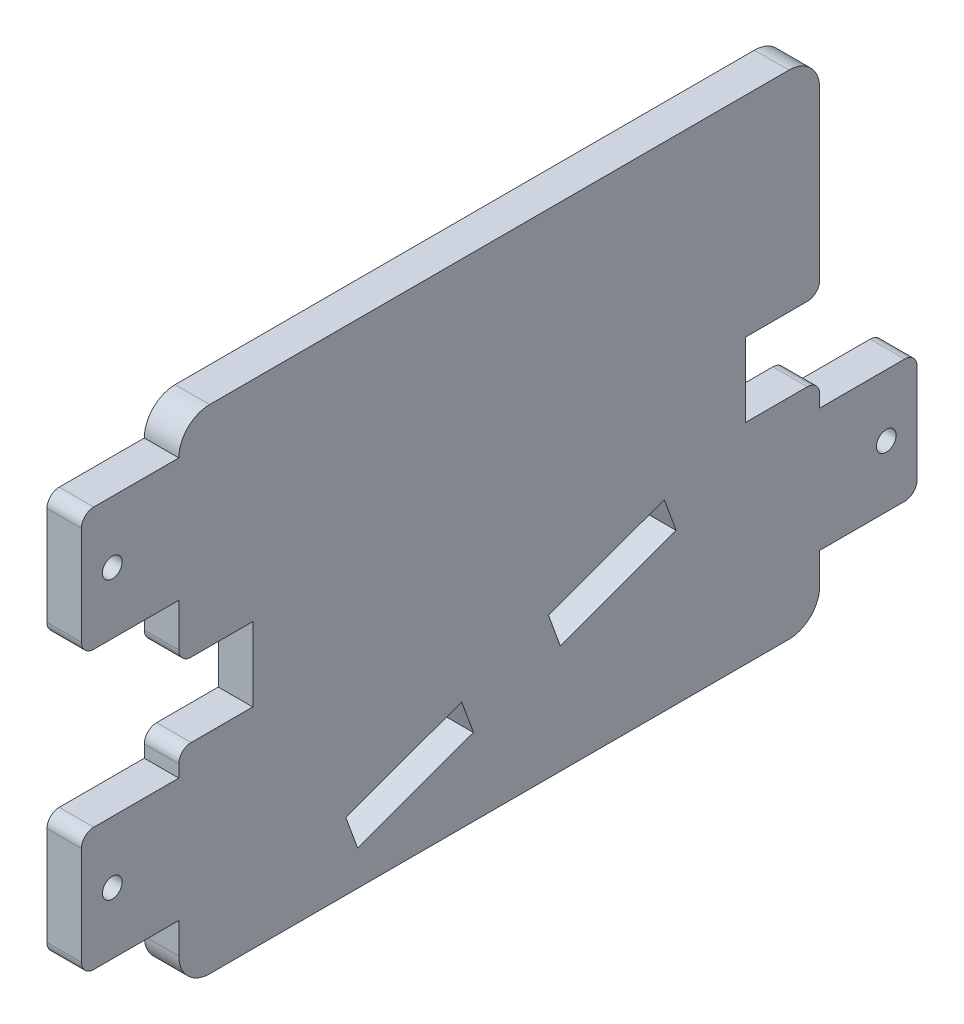
SolidWorks part; units mm, degrees
material "t5ハニカムプラダン"
ref_plane "正面" through (0, 0, 0) normal (0, 0, 1) x (1, 0, 0)
ref_plane "平面" through (0, 0, 0) normal (0, 1, 0) x (1, 0, 0)
ref_plane "右側面" through (0, 0, 0) normal (1, 0, 0) x (0, 0, -1)
sketch "ｽｹｯﾁ1" plane through (0, 0, 0) normal (1, 0, 0) x (0, 0, -1)
  line L0 (67.8, 25) -> (62.8, 25) construction
  line L1 (-52, 40) -> (52, 40)
  line L2 (-52, 40) -> (-52, -40)
  line L3 (-52, -40) -> (52, -40)
  line L4 (52, 40) -> (52, -40)
  line L5 (-52, 40) -> (52, -40) construction
  line L6 (-52, -40) -> (52, 40) construction
  line L7 (-67.8, 35) -> (-52, 35)
  line L8 (-67.8, 35) -> (-67.8, 15)
  line L9 (-67.8, 15) -> (-52, 15)
  line L10 (-52, 35) -> (-52, 15)
  line L11 (52, 35) -> (67.8, 35) construction
  line L12 (52, 35) -> (52, 15) construction
  line L13 (52, 15) -> (67.8, 15) construction
  line L14 (67.8, 35) -> (67.8, 15) construction
  line L15 (-67.8, 25) -> (-62.8, 25) construction
  line L16 (67.8, -20) -> (62.8, -20) construction
  line L17 (67.8, -30) -> (67.8, -10)
  line L18 (52, -10) -> (67.8, -10)
  line L19 (52, -30) -> (52, -10)
  line L20 (52, -30) -> (67.8, -30)
  line L21 (-52, -30) -> (-52, -10)
  line L22 (-67.8, -10) -> (-52, -10)
  line L23 (-67.8, -30) -> (-67.8, -10)
  line L24 (-67.8, -30) -> (-52, -30)
  line L25 (0, 0) -> (-52, 0) construction
  line L26 (0, 0) -> (0, -40) construction
  circle A0 centre (62.8, 25) radius 1.6 construction
  circle A1 centre (62.8, -20) radius 1.6
  circle A2 centre (-62.8, 25) radius 1.6
  circle A3 centre (-62.8, -20) radius 1.6
  point P0 (0, 0)
  dimension "D7" = 3.2
  dimension "D10" = 3.2
  dimension "D1" = 104
  dimension "D2" = 80
  dimension "D3" = 15.8
  dimension "D4" = 20
  dimension "D5" = 5
  dimension "D6" = 15.8
  dimension "D8" = 5
  dimension "D9" = 45
extrude "ﾎﾞｽ - 押し出し1" add sketch "ｽｹｯﾁ1" along normal blind 5.6 contours L4 L1 L2 L3 | L8 L9 L2 L7 | L23 L24 L2 L22 | L14 L11 L4 L13 A0 | L4 L20 L17 L18 A1 region at (0, 0, 0) region at (0, 25, 59.8243) region at (0, -20, -59.8243) region at (0, -20, 59.8243)
fillet "ﾌｨﾚｯﾄ1" radius 5 4 edges at (2.8, -40, -52) (2.8, -40, 52) (2.8, 40, -52) (2.8, 40, 52)
sketch "ｽｹｯﾁ3" plane through (5.6, 0, 0) normal (1, 0, 0) x (0, 0, -1)
  line L0 (-34.2931, -32.5) -> (-49, 7.9068) construction
  line L1 (-34.2931, -32.5) -> (54.9777, -0.0081) construction
  line L2 (-49, 7.9068) -> (40.2708, 40.3987) construction
  line L3 (54.9777, -0.0081) -> (40.2708, 40.3987) construction
  line L4 (-52, 15) -> (-52, -10) construction
  line L5 (-47, -40) -> (47, -40) construction
  line L6 (47, 40) -> (52, 40) construction
  line L7 (52, 40) -> (52, 35) construction
  line L8 (-24.8962, -29.0798) -> (-6.1024, -22.2394)
  line L9 (52, 40) -> (42, 40) construction
  line L10 (52, 40) -> (52, 50) construction
  line L11 (52, 50) -> (42, 50) construction
  line L12 (42, 40) -> (42, 50) construction
  line L13 (-24.8962, -29.0798) -> (-22.9809, -34.3421)
  line L14 (-6.1024, -22.2394) -> (-4.187, -27.5017)
  line L15 (-22.9809, -34.3421) -> (-4.187, -27.5017)
  line L16 (7.993, -17.1091) -> (26.7869, -10.2687)
  line L17 (7.993, -17.1091) -> (9.9083, -22.3714)
  line L18 (26.7869, -10.2687) -> (28.7022, -15.531)
  line L19 (9.9083, -22.3714) -> (28.7022, -15.531)
  arc A0 (52, 35) -> (47, 40) centre (47, 35) ccw construction
  dimension "D1" = 43
  dimension "D2" = 95
  dimension "D3" = 3
  dimension "D4" = 20
  dimension "D5" = 10
  dimension "D6" = 7.5
  dimension "D7" = 20
  dimension "D8" = 5.6
  dimension "D9" = 15
  dimension "D10" = 20
extrude "ｶｯﾄ - 押し出し1" cut sketch "ｽｹｯﾁ3" against normal through all
sketch "ｽｹｯﾁ4" plane through (5.6, 0, 0) normal (1, 0, 0) x (0, 0, -1)
  line L0 (-52, 15) -> (-52, -10) construction
  line L1 (-52, 6) -> (-40, 6)
  line L2 (-52, 6) -> (-52, -6)
  line L3 (-52, -6) -> (-40, -6)
  line L4 (-40, 6) -> (-40, -6)
  line L5 (52, 35) -> (52, -10) construction
  line L6 (40, 6) -> (52, 6)
  line L7 (40, 6) -> (40, -6)
  line L8 (40, -6) -> (52, -6)
  line L9 (52, 6) -> (52, -6)
  line L10 (-47, -40) -> (47, -40) construction
  dimension "D1" = 12
  dimension "D2" = 34
extrude "ｶｯﾄ - 押し出し2" cut sketch "ｽｹｯﾁ4" against normal through all
fillet "ﾌｨﾚｯﾄ2" radius 2 10 edges at (2.8, -30, -67.8) (2.8, -10, -67.8) (2.8, -30, 67.8) (2.8, -10, 67.8) (2.8, 15, 67.8) (2.8, 35, 67.8) (2.8, 6, -52) (2.8, -6, -52) (2.8, 6, 52) (2.8, -6, 52)
